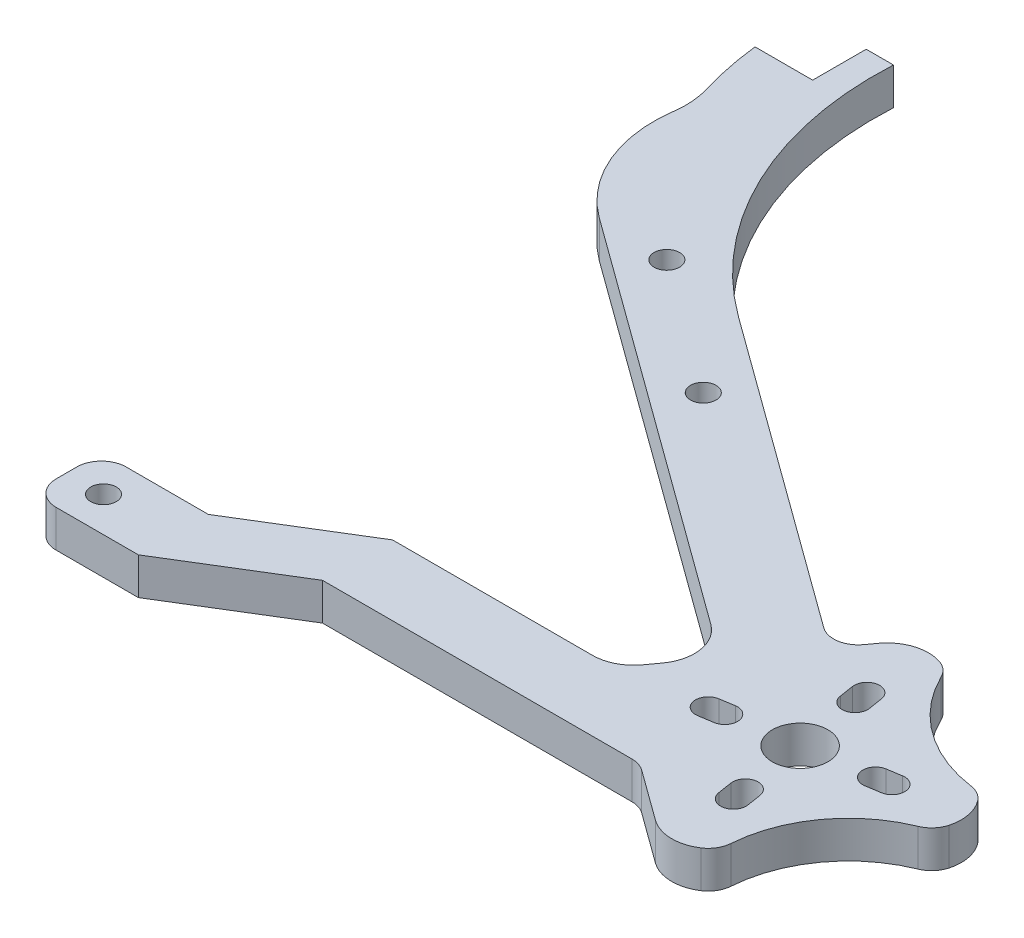
SolidWorks part; units mm, degrees
material "PPS"
ref_plane "前视基准面" through (0, 0, 0) normal (0, 0, 1) x (1, 0, 0)
ref_plane "上视基准面" through (0, 0, 0) normal (0, 1, 0) x (1, 0, 0)
ref_plane "右视基准面" through (0, 0, 0) normal (1, 0, 0) x (0, 0, -1)
sketch "草图3" plane through (0, 0, 0) normal (0, 1, 0) x (1, 0, 0)
  line L0 (0, 0) -> (35.4735, 0) construction
  line L1 (0, 0) -> (62.3757, -45.3186) construction
  line L2 (41.1319, -24.0128) -> (94.6944, -62.9282)
  line L3 (94.6944, -62.9282) -> (100.1314, -55.4448)
  line L4 (100.1314, -55.4448) -> (122.7839, -71.9028)
  line L5 (122.7839, -71.9028) -> (106.3259, -94.5552)
  line L6 (83.6734, -78.0972) -> (106.3259, -94.5552) construction
  line L9 (77.9994, -109.7251) -> (128.6275, -40.0415) construction
  line L11 (103.2286, -75) -> (90.242, -77.0569) construction
  line L13 (111.1302, -73.7485) -> (112.8586, -73.4748) construction
  line L14 (110.8877, -72.2176) -> (112.6161, -71.9438)
  line L15 (111.3726, -75.2794) -> (113.1011, -75.0057)
  line L16 (101.9772, -67.0985) -> (101.7034, -65.37) construction
  line L17 (103.5081, -66.856) -> (103.2343, -65.1276)
  line L18 (100.4463, -67.341) -> (100.1725, -65.6125)
  line L19 (95.3271, -76.2515) -> (93.5987, -76.5252) construction
  line L20 (95.5696, -77.7824) -> (93.8412, -78.0562)
  line L21 (95.0847, -74.7206) -> (93.3562, -74.9943)
  line L22 (104.4801, -82.9015) -> (104.7539, -84.63) construction
  line L23 (102.9492, -83.144) -> (103.223, -84.8724)
  line L24 (106.011, -82.659) -> (106.2848, -84.3875)
  line L36 (68.8077, -72) -> (90.242, -72) construction
  line L49 (89.1104, -70.6138) -> (83.6734, -78.0972)
  line L50 (35.5479, -31.6984) -> (89.1104, -70.6138)
  line L51 (83.6734, -78.0972) -> (30, -78.0972) construction
  line L52 (30, -78.0972) -> (30, -86.5972) construction
  line L53 (30, -86.5972) -> (95.3727, -86.5972) construction
  line L54 (95.3727, -86.5972) -> (106.3259, -94.5552)
  line L55 (83.6734, -78.0972) -> (56.8367, -78.0972)
  line L56 (95.3727, -86.5972) -> (56.8367, -86.5972)
  line L57 (56.8367, -78.0972) -> (42.9738, -86.5972)
  line L58 (42.9738, -86.5972) -> (30, -86.5972)
  line L59 (56.8367, -86.5972) -> (42.9738, -95.0972)
  line L60 (30, -86.5972) -> (30, -95.0972)
  line L61 (30, -95.0972) -> (42.9738, -95.0972)
  circle A5 centre (103.2286, -75) radius 3.375
  arc A6 (110.8877, -72.2176) -> (111.3726, -75.2794) centre (111.1302, -73.7485) ccw
  arc A7 (113.1011, -75.0057) -> (112.6161, -71.9438) centre (112.8586, -73.4748) ccw
  arc A8 (103.5081, -66.856) -> (100.4463, -67.341) centre (101.9772, -67.0985) cw
  arc A9 (100.1725, -65.6125) -> (103.2343, -65.1276) centre (101.7034, -65.37) cw
  arc A10 (95.5696, -77.7824) -> (95.0847, -74.7206) centre (95.3271, -76.2515) ccw
  arc A11 (93.3562, -74.9943) -> (93.8412, -78.0562) centre (93.5987, -76.5252) ccw
  arc A12 (102.9492, -83.144) -> (106.011, -82.659) centre (104.4801, -82.9015) cw
  arc A13 (106.2848, -84.3875) -> (103.223, -84.8724) centre (104.7539, -84.63) cw
  arc A16 (41.1319, -24.0128) -> (35.5479, -31.6984) centre (38.3399, -27.8556) ccw
  circle A17 centre (103.2286, -75) radius 66.25 construction
  circle A18 centre (44.0442, -32) radius 1.55
  circle A19 centre (60.2246, -43.7557) radius 1.55
  circle A20 centre (34.5, -90.8472) radius 1.55
  point P11 (114.5549, -83.229)
  point P20 (111.9944, -73.6116)
  point P27 (101.8403, -66.2343)
  point P35 (94.4629, -76.3884)
  point P42 (104.617, -83.7657)
  point P54 (94.9997, -86.3262)
  point P69 (30, -90.8472)
  dimension "D2" = 45
  dimension "D3" = 6.75
  dimension "D4" = 1.55
  dimension "D7" = 14
  dimension "D11" = 132.5
  dimension "D12" = 3.1
  dimension "D16" = 3.1
  dimension "D1" = 36
  dimension "D5" = 1.75
  dimension "D6" = 8
  dimension "D8" = 14
  dimension "D9" = 4.75
  dimension "D10" = 75
  dimension "D13" = 32
  dimension "D14" = 20
  dimension "D15" = 8.5
  dimension "D17" = 34.5
  dimension "D18" = 4.5
  dimension "D19" = 90.8472
  dimension "D22" = 72
extrude "凸台-拉伸1" add sketch "草图3" along normal blind 4.5
fillet "圆角-美观1" radius 5 5 edges at (100.1314, 2.25, 55.4448) (122.7839, 2.25, 71.9028) (89.1104, 2.25, 70.6138) (106.3259, 2.25, 94.5552) (83.6734, 2.25, 78.0972)
sketch "草图4" plane through (0, 4.5, 0) normal (0, 1, 0) x (1, 0, 0)
  line L0 (104.1765, -58.3837) -> (118.7388, -68.9638)
  line L1 (119.8449, -75.9478) -> (109.2648, -90.5101)
  line L3 (103.2286, -75) -> (124.6569, -90.5685) construction
  line L4 (103.2286, -75) -> (89.033, -94.5387) construction
  line L5 (87.7185, -81.0362) -> (102.2808, -91.6163)
  arc A2 (102.2808, -91.6163) -> (87.7185, -81.0362) centre (86.1651, -98.4859) ccw
  arc A8 (118.7388, -68.9638) -> (104.1765, -58.3837) centre (120.2922, -51.5141) cw
  arc A9 (119.8449, -75.9478) -> (109.2648, -90.5101) centre (124.6569, -90.5685) ccw
  line M2 (118.7388, -68.9638) -> (104.1765, -58.3837)
  line M12 (109.2648, -90.5101) -> (119.8449, -75.9478)
extrude "圆弧-美观2" cut sketch "草图4" against normal up to next contours A8 M2 | A9 M12 region at (110.8688, 4.5, 64.4842) region at (113.6066, 4.5, 82.54)
fillet "圆角-美观3" radius 3 8 edges at (104.1765, 2.25, 58.3837) (118.7388, 2.25, 68.9638) (119.8449, 2.25, 75.9478) (94.6944, 2.25, 62.9282) (109.2648, 2.25, 90.5101) (30, 2.25, 95.0972) (95.3727, 2.25, 86.5972) (30, 2.25, 86.5972)
sketch "草图5" plane through (0, 0, 0) normal (0, 1, 0) x (1, 0, 0)
  line L0 (0, 0) -> (158.8801, 0) construction
  line L1 (0, 0) -> (0, -78.2587) construction
  line L2 (29.255, -13.8932) -> (40.1931, -23.471) construction
  line L3 (27.0025, -4.25) -> (34, -4.25)
  line L4 (34, -4.25) -> (34, 2.25)
  line L5 (34, -3.25) -> (26.9026, -3.25) construction
  line L6 (34, 3.25) -> (34, -3.25) construction
  line L7 (37.3772, 3.25) -> (34, 3.25) construction
  line L8 (41.1319, -24.0128) -> (54.395, -33.649)
  line L9 (34, 2.25) -> (37.3109, 2.25)
  line L10 (35.5479, -31.6984) -> (85.0653, -67.6749) construction
  line L11 (41.1319, -24.0128) -> (35.5479, -31.6984)
  arc A0 (26.9026, -3.25) -> (28.5167, -11.6611) centre (68.8233, 0.4342) ccw construction
  arc A5 (41.1319, -24.0128) -> (40.1931, -23.471) centre (38.2952, -27.8445) ccw
  arc A7 (40.1931, -23.471) -> (35.5479, -31.6984) centre (38.3022, -27.8285) ccw construction
  arc A8 (35.5479, -31.6984) -> (28.8424, -15.919) centre (45.3379, -18.2237) cw
  arc A9 (28.8424, -15.919) -> (28.5167, -11.6611) centre (18.9386, -14.5353) ccw
  arc A11 (37.3772, 3.25) -> (54.395, -33.649) centre (78.8424, 0) ccw
  arc A12 (27.0025, -4.25) -> (28.5167, -11.6611) centre (68.8233, 0.4342) ccw
  arc A13 (29.8202, 19.4008) -> (29.8202, -19.4008) centre (91.9966, 0) ccw construction
  arc A14 (54.395, 33.649) -> (54.395, -33.649) centre (78.8424, 0) ccw construction
  arc A15 (29.9602, 19.3706) -> (29.9602, -19.3706) centre (67.3193, 0) ccw construction
  dimension "D1" = 3.25
  dimension "D2" = 3.25
  dimension "D3" = 34
  dimension "D4" = 1
  dimension "D5" = 1
extrude "机臂配合防旋转" add sketch "草图5" along normal up to surface (4.5 mm away) contours L7 A0 A9 A8 A7 A5 L8 region at (35.1434, 0, 16.2105) up to face at (60.2246, 4.5, 45.3057)
